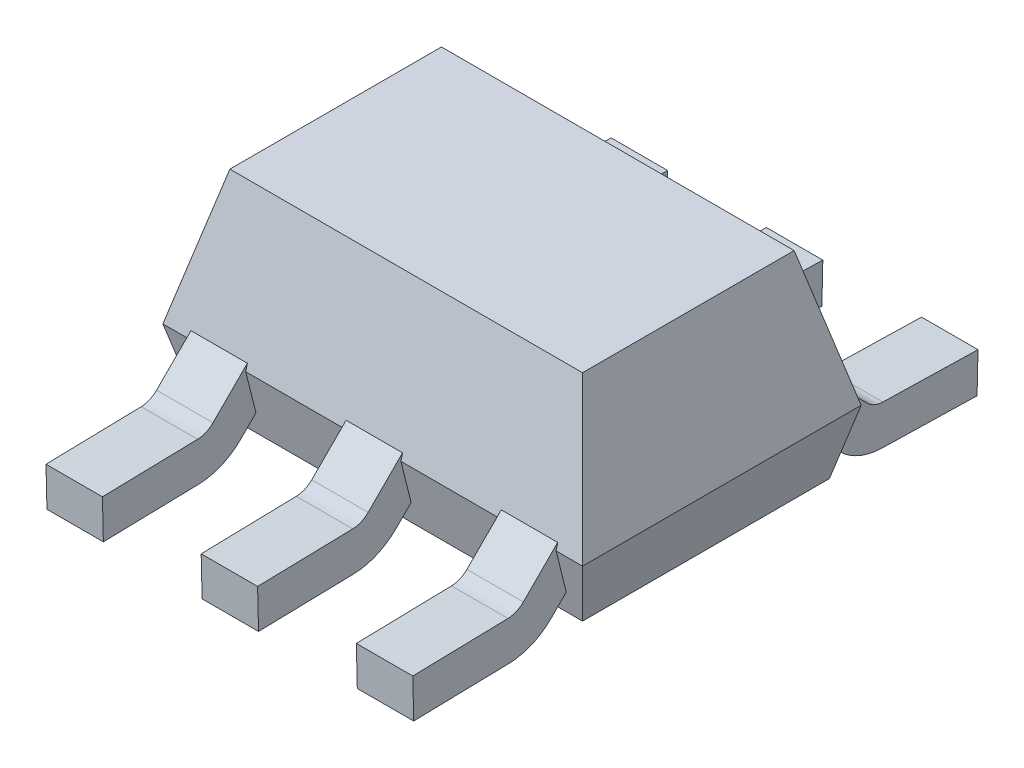
SolidWorks part; units mm, degrees
material "Pure Silver"
ref_plane "Front Plane" through (0, 0, 0) normal (0, 0, 1) x (1, 0, 0)
ref_plane "Top Plane" through (0, 0, 0) normal (0, 1, 0) x (1, 0, 0)
ref_plane "Right Plane" through (0, 0, 0) normal (1, 0, 0) x (0, 0, -1)
sketch "Sketch1" plane through (0, 0, 0) normal (0, 1, 0) x (1, 0, 0)
  line L1 (-1.5, 1) -> (1.5, 1)
  line L2 (-1.5, 1) -> (-1.5, -1)
  line L3 (-1.5, -1) -> (1.5, -1)
  line L4 (1.5, 1) -> (1.5, -1)
  line L6 (1.5, -1) -> (-1.5, 1) construction
  dimension "D1" = 3
  dimension "D3" = 2
extrude "IC" add sketch "Sketch1" along normal blind 1.4
chamfer "IC TC" distance 1 distance2 0.25 4 edges at (-1.5, 1.4, 0) (0, 1.4, -1) (1.5, 1.4, 0) (0, 1.4, 1) first distance on face at (-1.5, 0.7, 0) first distance on face at (0, 0.7, -1) first distance on face at (1.5, 0.7, 0) first distance on face at (0, 0.7, 1)
chamfer "IC BC" distance 0.125 distance2 0.5 4 edges at (0, 0, 1) (-1.5, 0, 0) (0, 0, -1) (1.5, 0, 0) first distance on face at (0, 0, 0)
sketch "LEG PROFILE" plane through (0, 0, 0) normal (1, 0, 0) x (0, 0, -1)
  line L0 (0, 0.55) -> (-0.6, 0.55)
  line L1 (0, 0.88) -> (0, -0.88) construction
  line L2 (-0.8121, 0.4621) -> (-1.1206, 0.1536)
  line L3 (-1.3066, 0.0669) -> (-1.5, 0.05)
  line L4 (1.0862, 0) -> (-1.0862, 0) construction
  arc A0 (-0.6, 0.55) -> (-0.8121, 0.4621) centre (-0.6, 0.25) ccw
  arc A1 (-1.1206, 0.1536) -> (-1.3066, 0.0669) centre (-1.3327, 0.3658) cw
  dimension "D4" = 0.3
  dimension "D1" = 0.55
  dimension "D2" = 1.5
  dimension "D3" = 0.05
  dimension "D5" = 45
  dimension "D6" = 5
  dimension "D7" = 0.6
sketch "Sketch3" plane through (0, 0, 0) normal (1, 0, 0) x (0, 0, -1)
  line L0 (0, 0.55) -> (0.6, 0.55)
  line L1 (0, 0.88) -> (0, -0.88) construction
  line L2 (0.8121, 0.4621) -> (1.1206, 0.1536)
  line L3 (1.3257, 0.0659) -> (2, 0.05)
  line L4 (0, 0.55) -> (-0.6, 0.55) construction
  arc A0 (1.1206, 0.1536) -> (1.3257, 0.0659) centre (1.3327, 0.3658) ccw
  arc A1 (0.6, 0.55) -> (0.8121, 0.4621) centre (0.6, 0.25) cw
  dimension "D2" = 0.3
  dimension "D1" = 2
  dimension "D3" = 0.6
  dimension "D4" = 45
extrude "LEG EXTRUDED" add sketch "Sketch3" along normal mid plane 0.4 thin thin type mid plane wall 0.28
pattern_linear "LEG P" count 2 spacing 1.1 along (-1, 0, 0) count 2 spacing 1.1 along (1, 0, 0) of "LEG EXTRUDED" pattern seed only yes
mirror "Mirror1" about plane through (0, 0, 0) normal (0, 0, 1) of "LEG P", "LEG EXTRUDED"
